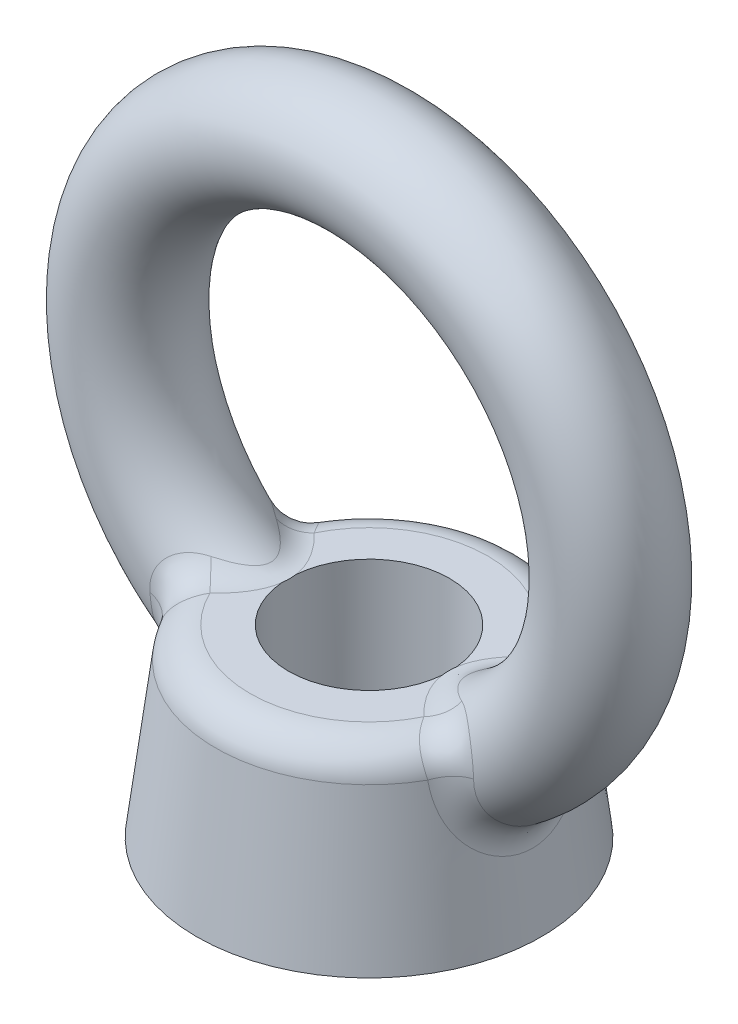
SolidWorks part; units mm, degrees
material "Латунь"
ref_plane "Спереди" through (0, 0, 0) normal (0, 0, 1) x (1, 0, 0)
ref_plane "Сверху" through (0, 0, 0) normal (0, 1, 0) x (1, 0, 0)
ref_plane "Справа" through (0, 0, 0) normal (1, 0, 0) x (0, 0, -1)
sketch "Эскиз2" plane through (0, 0, 0) normal (0, 0, 1) x (1, 0, 0)
  line L1 (0, -8.5141) -> (0, 57.16) construction
  line L5 (0, 0) -> (15, 0)
  line L6 (15, 0) -> (13.3285, 13.3721)
  line L7 (10.3517, 16) -> (0, 16)
  line L8 (0, 16) -> (0, 0)
  arc A0 (13.3285, 13.3721) -> (10.3517, 16) centre (10.3517, 13) ccw
  point P10 (13, 16)
  dimension "D4" = 3
  dimension "D1" = 30
  dimension "D2" = 26
  dimension "D3" = 16
revolve "Повернуть1" add sketch "Эскиз2" angle 360 about L1
sketch "Эскиз3" plane through (0, 0, 0) normal (1, 0, 0) x (0, 0, -1)
  circle A0 centre (0, 11) radius 5
  dimension "D2" = 10
  dimension "D1" = 11
sketch "Эскиз4" plane through (0, 0, 0) normal (0, 0, 1) x (1, 0, 0)
  line L5 (-19.2796, 15.1447) -> (-30.0344, 34.6989)
  line L6 (-20.396, 51) -> (20.396, 51)
  line L7 (0, 0) -> (0, 60.7) construction
  line L8 (19.2796, 15.1447) -> (30.0344, 34.6989)
  line L9 (-12.2698, 11) -> (12.2698, 11)
  arc A4 (-20.396, 51) -> (-30.0344, 34.6989) centre (-20.396, 40) ccw
  arc A5 (30.0344, 34.6989) -> (20.396, 51) centre (20.396, 40) ccw
  arc A6 (12.2698, 11) -> (19.2796, 15.1447) centre (12.2698, 19) ccw
  arc A7 (-19.2796, 15.1447) -> (-12.2698, 11) centre (-12.2698, 19) ccw
  point P5 (-39, 51)
  point P13 (-17, 11)
  point P14 (17, 11)
  point P15 (39, 51)
  dimension "D1" = 11
  dimension "D6" = 8
  dimension "D2" = 78
  dimension "D3" = 34
  dimension "D4" = 40
  dimension "D5" = 11
sweep "По траектории1" [suppressed] add profiles "Эскиз3" path "Эскиз4"
fillet "Скругление1" [suppressed] radius 3
sketch "Эскиз7" plane through (0, 0, 0) normal (1, 0, 0) x (0, 0, -1)
  line L0 (-13.2998, 30) -> (10.6957, 30) construction
  line L1 (-15, 0) -> (15, 0) construction
  circle A0 centre (0, 9) radius 5
  point P6 (-13.2998, 30)
  point P7 (10.6957, 30)
  point P8 (0, 0)
  dimension "D1" = 10
  dimension "D2" = 9
  dimension "D3" = 21
revolve "Повернуть2" add sketch "Эскиз7" angle 360 about L0
fillet "Скругление2" radius 3 8 edges at (-11.5394, 15.2159, -4.4674) (-11.6334, 15.1075, 4.5366) (11.5394, 15.2159, 4.4674) (11.6334, 15.1075, -4.5366) (-13.9869, 8.0892, 0.2344) (13.9869, 8.0892, -0.2344) (-7.7544, 16, -0.2024) (21.8971, 16, -0.3153)
hole_wizard "Отверстие обработанное метчиком M161" positions "Эскиз5" profile "Эскиз6" tap size "M16" standard "ISO" end condition up to next
sketch "Эскиз5" plane through (0, 16, 0) normal (0, 1, 0) x (1, 0, 0)
  point P0 (0, 0)
sketch "Эскиз6" plane through (0, 16, 0) normal (1, 0, 0) x (0, 0, 1)
  line L0 (0, 0) -> (0, 16)
  line L1 (0, 16) -> (9, 16)
  line L2 (7, 14) -> (7, 0)
  line L5 (7, 0) -> (0, 0)
  line L7 (9, 16) -> (7, 14)
  line L8 (-9, 16) -> (-7, 14) construction
  line L11 (0, -6.35) -> (0, 107.95) construction
  dimension "Диаметр проходного сверла" = 14
  dimension "Глубина проходного сверла" = 16
  dimension "Диаметр задней зенковки" = 18
  dimension "Угол задней зенковки" = 90
cosmetic thread "Отверстие резьбы2" parameters "D2"=16
